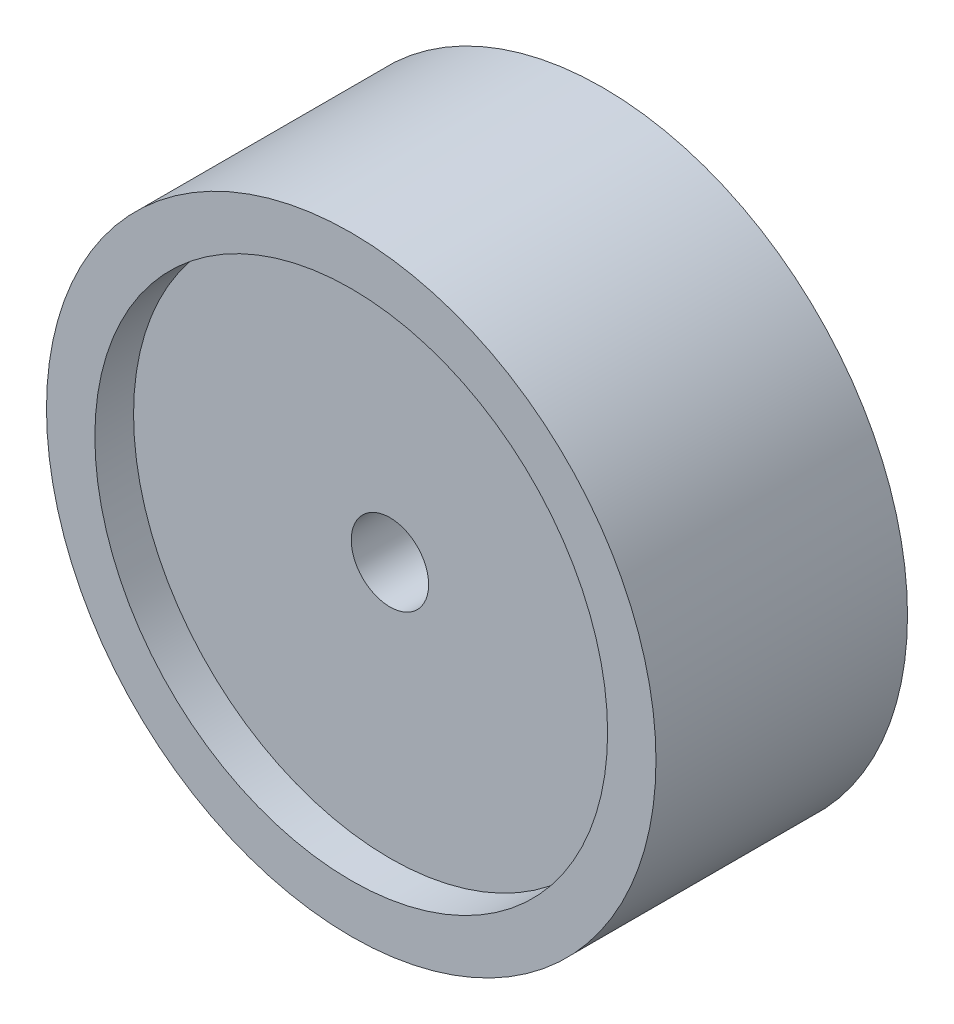
SolidWorks part; units mm, degrees
ref_plane "Plan de face" through (0, 0, 0) normal (0, 0, 1) x (1, 0, 0)
ref_plane "Plan de dessus" through (0, 0, 0) normal (0, 1, 0) x (1, 0, 0)
ref_plane "Plan de droite" through (0, 0, 0) normal (1, 0, 0) x (0, 0, -1)
sketch "Esquisse1" plane through (0, 0, 0) normal (0, 0, 1) x (1, 0, 0)
  circle A0 centre (0, 0) radius 31.5
  dimension "D1" = 63
extrude "Boss.-Extru.1" add sketch "Esquisse1" along normal blind 26
sketch "Esquisse2" plane through (0, 0, 26) normal (0, 0, 1) x (1, 0, 0)
  circle A0 centre (0, 0) radius 4
  dimension "D1" = 8
extrude "Enlèv. mat.-Extru.1" cut sketch "Esquisse2" against normal through all
sketch "Esquisse3" plane through (0, 0, 26) normal (0, 0, 1) x (1, 0, 0)
  circle A0 centre (0, 0) radius 26.5
  dimension "D1" = 53
extrude "Enlèv. mat.-Extru.2" cut sketch "Esquisse3" against normal blind 4
